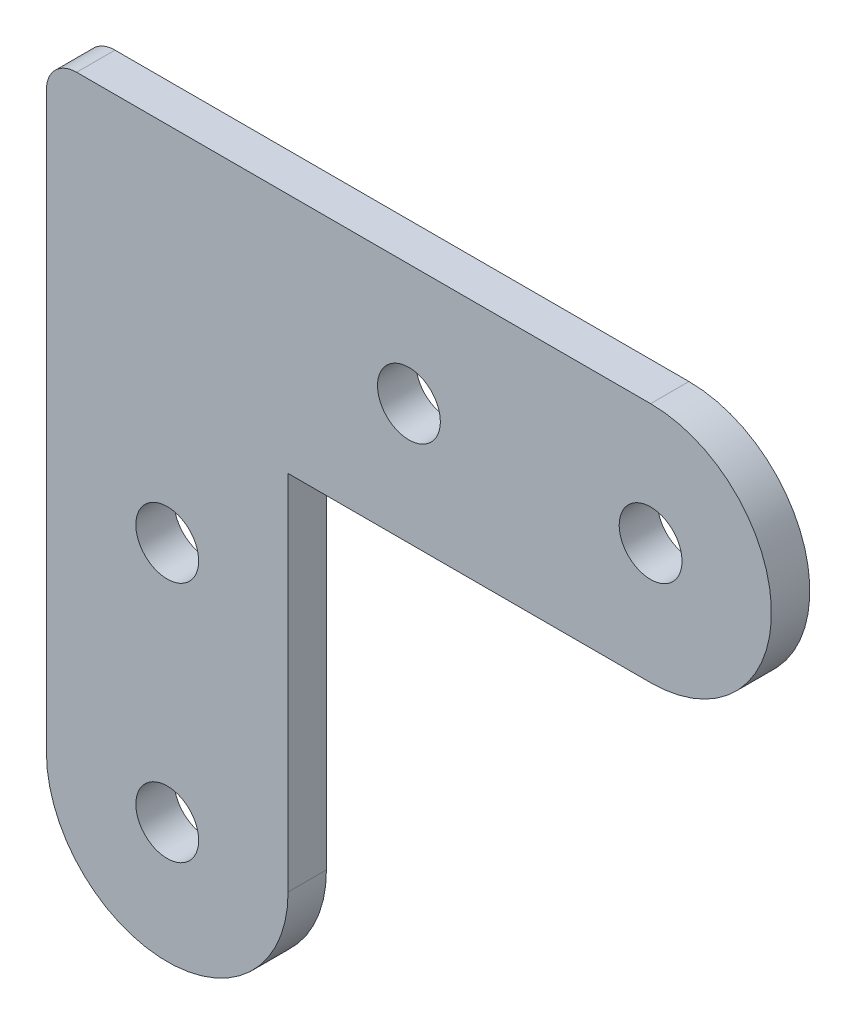
SolidWorks part; units mm, degrees
note: '?' marks a value the reader was unsure of.
ref_plane "Front Plane" through (0, 0, 0) normal (0, 0, 1) x (1, 0, 0)
ref_plane "Top Plane" through (0, 0, 0) normal (0, 1, 0) x (1, 0, 0)
ref_plane "Right Plane" through (0, 0, 0) normal (1, 0, 0) x (0, 0, -1)
ref_plane "Plane1" through (0, 0, -167.2715) normal (0, 0, -1) x (-1, 0, 0)
sketch "Sketch11" plane through (0, 0, -167.2715) normal (0, 0, -1) x (-1, 0, 0)
  line L0 (395.3161, 315.3097) -> (425.3161, 315.3097)
  line L1 (425.3161, 315.3097) -> (425.3161, 285.3097)
  line L2 (445.3161, 285.3097) -> (445.3161, 332.8097)
  line L3 (442.8161, 335.3097) -> (395.3161, 335.3097)
  arc A0 (395.3161, 335.3097) -> (395.3161, 315.3097) centre (395.3161, 325.3097) ccw
  arc A1 (425.3161, 285.3097) -> (445.3161, 285.3097) centre (435.3161, 285.3097) ccw
  arc A2 (445.3161, 332.8097) -> (442.8161, 335.3097) centre (442.8161, 332.8097) ccw
base flange "Base-Flange1" sketch "Sketch11" thickness 3.175 reverse thickness direction yes parameters "D1"=0
hole_wizard "Ø5.2 (5.2) Diameter Hole1" positions "Sketch17" profile "Sketch16" hole size "Ø5.2" standard "ANSI Metric"
sketch "Sketch17" plane through (0, 0, -167.2715) normal (0, 0, -1) x (-1, 0, 0)
  point P0 (435.3161, 285.3097)
  point P1 (395.3161, 325.3097)
  point P2 (415.3161, 325.3097)
  point P3 (435.3161, 305.3369)
sketch "Sketch16" plane through (-435.3161, 285.3097, -167.2715) normal (1, 0, 0) x (0, 1, 0)
  line L0 (0, 0) -> (0, 3.175)
  line L1 (0, 3.175) -> (2.6, 3.175)
  line L2 (2.6, 3.175) -> (2.6, 0)
  line L5 (2.6, 0) -> (0, 0)
  line L11 (0, -6.35) -> (0, 107.95) construction
  dimension "Thru Hole Dia." = 5.2
  dimension "Thru Hole Depth" = 3.175
ref_point "Point1"
ref_axis "Axis1" through (-395.3161, 325.3097, -164.0965) along (0, 0, -1)?
ref_axis "Axis2" through (-415.3161, 325.3097, -164.0965) along (0, 0, -1)?
ref_axis "Axis3" through (-435.3161, 305.3369, -164.0965) along (0, 0, -1)?
ref_axis "Axis4" through (-435.3161, 285.3097, -164.0965) along (0, 0, -1)?
sketch "Bend-Lines4" plane through (0, 0, 0) normal (0, 1, 0) x (1, 0, 0)
sketch "Bounding-Box4" plane through (0, 0, 0) normal (0, 1, 0) x (1, 0, 0)
sheet metal parameters "Sheet-Metal(5)" thickness 3.175 parameters "D1"=0
flat pattern "Flat-Pattern(5)" [suppressed]
sketch "Bend-Lines5" plane through (0, 0, 0) normal (0, 1, 0) x (1, 0, 0)
sketch "Bounding-Box5" [suppressed] plane through (0, 0, 0) normal (0, 1, 0) x (1, 0, 0)
sheet metal parameters "Sheet-Metal(6)" thickness 3.175 parameters "D1"=0
flat pattern "Flat-Pattern(5)"
sketch "Bend-Lines5" plane through (0, 0, 0) normal (0, 1, 0) x (1, 0, 0)
sketch "Bounding-Box5" [suppressed] plane through (0, 0, 0) normal (0, 1, 0) x (1, 0, 0)
